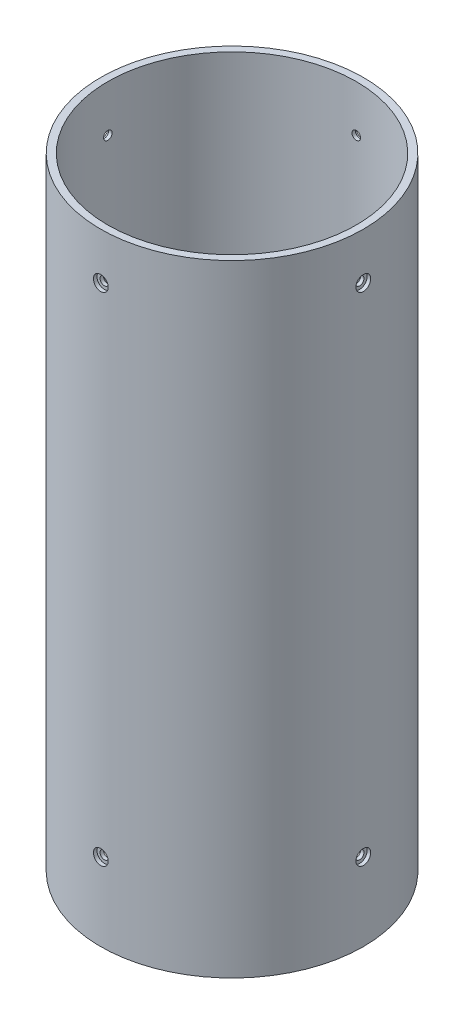
SolidWorks part; units mm, degrees
material "Hexcel AS4C (3000 Filaments)"
ref_plane "Front Plane" through (0, 0, 0) normal (0, 0, 1) x (1, 0, 0)
ref_plane "Top Plane" through (0, 0, 0) normal (0, 1, 0) x (1, 0, 0)
ref_plane "Right Plane" through (0, 0, 0) normal (1, 0, 0) x (0, 0, -1)
sketch "Sketch1" plane through (0, 0, 0) normal (0, 1, 0) x (1, 0, 0)
  circle A0 centre (0, 0) radius 50.8
  dimension "D1" = 101.6
extrude "Body Extrusion" add sketch "Sketch1" along normal blind 254 thin thin type one direction wall 2.921
ref_plane "Plane1" through (0, 0, 53.721) normal (0, 0, 1) x (1, 0, 0)
sketch "Sketch2" plane through (0, 0, 53.721) normal (0, 0, 1) x (1, 0, 0)
  line L0 (0, 254) -> (0, 0) construction
  line L1 (53.721, 254) -> (-53.721, 254) construction
  line L3 (50.8, 254) -> (-50.8, 254) construction
  circle A0 centre (0, 234.95) radius 1.7526
  dimension "D1" = 3.5052
  dimension "D2" = 19.05
extrude "Upper Bulkhead Holes" cut sketch "Sketch2" against normal up to next
pattern_circular "Upper Bulkhead Hole Pattern" count 4 over 360 about axis through (0, 254, 0) along (0, -1, 0) of "Upper Bulkhead Holes"
sketch "Sketch3" plane through (0, 0, 53.721) normal (0, 0, 1) x (1, 0, 0)
  line L0 (0, 254) -> (0, 0) construction
  line L1 (53.721, 254) -> (-53.721, 254) construction
  line L2 (50.8, 254) -> (-50.8, 254) construction
  circle A0 centre (0, 31.75) radius 1.7526
  dimension "D1" = 3.5052
  dimension "D2" = 31.75
  dimension "D3" = 222.25
extrude "Lower Bulkhead Holes" cut sketch "Sketch3" against normal up to next
pattern_circular "Lower Bulkhead Hole Pattern" count 4 over 360 about axis through (0, 254, 0) along (0, -1, 0) of "Lower Bulkhead Holes" reverse direction yes
sketch "Sketch4" plane through (0, 0, 53.721) normal (0, 0, 1) x (1, 0, 0)
  line L0 (0, 254) -> (0, 0) construction
  line L1 (50.8, 254) -> (-50.8, 254) construction
  line L2 (-50.8, 0) -> (50.8, 0) construction
  circle A0 centre (0, 234.95) radius 3.0226
  circle A1 centre (0, 31.75) radius 3.0226
  circle A2 centre (0, 31.75) radius 1.7526 construction
  circle A3 centre (0, 234.95) radius 1.7526 construction
  dimension "D1" = 1.27
  dimension "D2" = 1.27
extrude "Countersink" cut sketch "Sketch4" against normal blind 1.524
pattern_circular "Countersink Pattern" count 4 over 360 about axis through (0, 254, 0) along (0, -1, 0) of "Countersink"
equation "\"D2@Sketch4\"=\"D1@Sketch4\""
